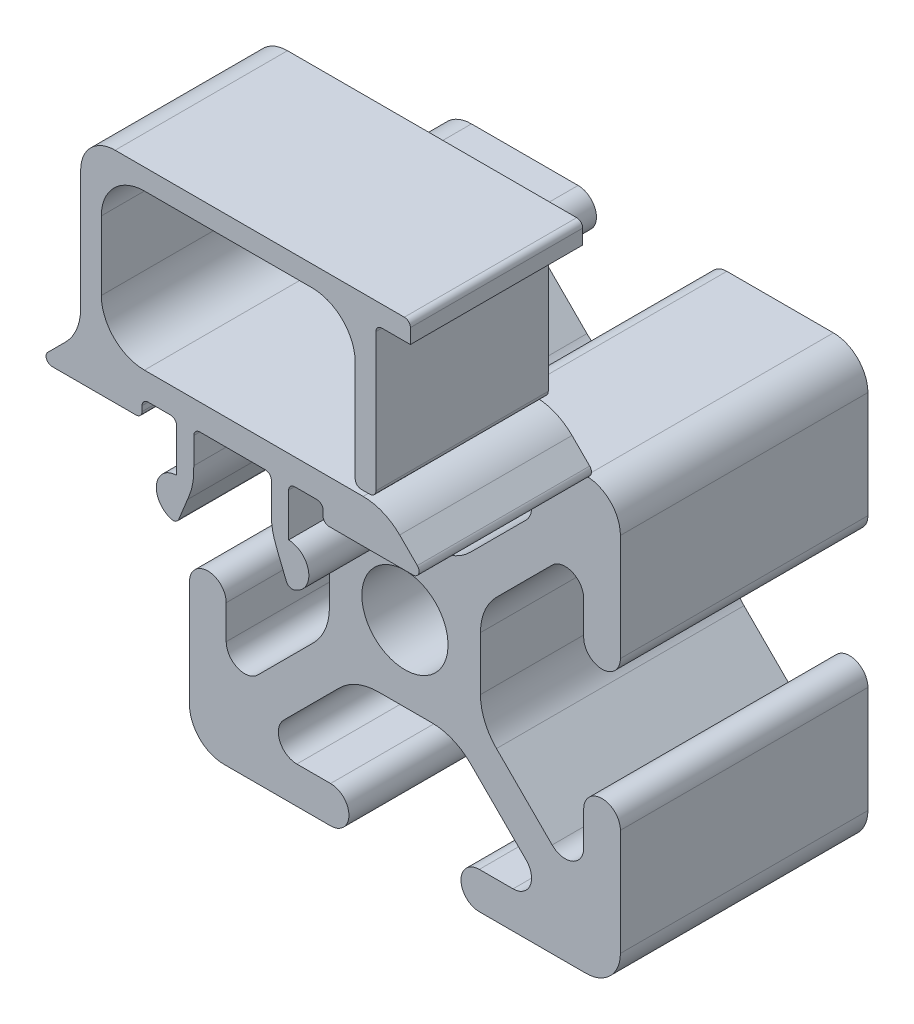
SolidWorks part; units mm, degrees
ref_plane "Front Plane" through (0, 0, 0) normal (0, 0, 1) x (1, 0, 0)
ref_plane "Top Plane" through (0, 0, 0) normal (0, 1, 0) x (1, 0, 0)
ref_plane "Right Plane" through (0, 0, 0) normal (1, 0, 0) x (0, 0, -1)
sketch "Sketch1" plane through (0, 0, 0) normal (0, 1, 0) x (1, 0, 0)
  line L0 (0, 0) -> (0, 14.3598)
other "25 series extrusions 25-2525(1)" corner treatment butt1
ref_plane "Plane1" through (0, 0, 0) normal (0, 0, -1) x (-1, 0, 0)
sketch "Sketch11" plane through (0, 0, 0) normal (0, 0, -1) x (-1, 0, 0)
  line L0 (12.5, -10.5) -> (12.5, -4.315)
  line L1 (10.37, -4.315) -> (10.37, -6.2728)
  line L2 (8.5396, -7.031) -> (5.311, -3.8024)
  line L3 (4.3811, -1.5573) -> (4.3811, 1.5573)
  line L4 (5.311, 3.8024) -> (8.5396, 7.031)
  line L5 (10.37, 6.2728) -> (10.37, 4.315)
  line L6 (12.5, 4.315) -> (12.5, 10.5)
  line L7 (10.5, 12.5) -> (4.315, 12.5)
  line L8 (4.315, 10.37) -> (6.2728, 10.37)
  line L9 (7.031, 8.5396) -> (3.8024, 5.311)
  line L10 (1.5573, 4.3811) -> (-1.5573, 4.3811)
  line L11 (-3.8024, 5.311) -> (-7.031, 8.5396)
  line L12 (-6.2728, 10.37) -> (-4.315, 10.37)
  line L13 (-4.315, 12.5) -> (-10.5, 12.5)
  line L14 (-12.5, 10.5) -> (-12.5, 4.315)
  line L15 (-10.37, 4.315) -> (-10.37, 6.2728)
  line L16 (-8.5396, 7.031) -> (-5.311, 3.8024)
  line L17 (-4.3811, 1.5573) -> (-4.3811, -1.5573)
  line L18 (-5.311, -3.8024) -> (-8.5396, -7.031)
  line L19 (-10.37, -6.2728) -> (-10.37, -4.315)
  line L20 (-12.5, -4.315) -> (-12.5, -10.5)
  line L21 (-10.5, -12.5) -> (-4.315, -12.5)
  line L22 (-4.315, -10.37) -> (-6.2728, -10.37)
  line L23 (-7.031, -8.5396) -> (-3.8024, -5.311)
  line L24 (-1.5573, -4.3811) -> (1.5573, -4.3811)
  line L25 (3.8024, -5.311) -> (7.031, -8.5396)
  line L26 (6.2728, -10.37) -> (4.315, -10.37)
  line L27 (4.315, -12.5) -> (10.5, -12.5)
  circle A0 centre (0, 0) radius 2.5
  arc A1 (10.5, -12.5) -> (12.5, -10.5) centre (10.5, -10.5) ccw
  arc A2 (12.5, -4.315) -> (10.37, -4.315) centre (11.435, -4.315) ccw
  arc A3 (8.5396, -7.031) -> (10.37, -6.2728) centre (9.2978, -6.2728) ccw
  arc A4 (4.3811, -1.5573) -> (5.311, -3.8024) centre (7.5561, -1.5573) ccw
  arc A5 (5.311, 3.8024) -> (4.3811, 1.5573) centre (7.5561, 1.5573) ccw
  arc A6 (10.37, 6.2728) -> (8.5396, 7.031) centre (9.2978, 6.2728) ccw
  arc A7 (10.37, 4.315) -> (12.5, 4.315) centre (11.435, 4.315) ccw
  arc A8 (12.5, 10.5) -> (10.5, 12.5) centre (10.5, 10.5) ccw
  arc A9 (4.315, 12.5) -> (4.315, 10.37) centre (4.315, 11.435) ccw
  arc A10 (7.031, 8.5396) -> (6.2728, 10.37) centre (6.2728, 9.2978) ccw
  arc A11 (1.5573, 4.3811) -> (3.8024, 5.311) centre (1.5573, 7.5561) ccw
  arc A12 (-3.8024, 5.311) -> (-1.5573, 4.3811) centre (-1.5573, 7.5561) ccw
  arc A13 (-6.2728, 10.37) -> (-7.031, 8.5396) centre (-6.2728, 9.2978) ccw
  arc A14 (-4.315, 10.37) -> (-4.315, 12.5) centre (-4.315, 11.435) ccw
  arc A15 (-10.5, 12.5) -> (-12.5, 10.5) centre (-10.5, 10.5) ccw
  arc A16 (-12.5, 4.315) -> (-10.37, 4.315) centre (-11.435, 4.315) ccw
  arc A17 (-8.5396, 7.031) -> (-10.37, 6.2728) centre (-9.2978, 6.2728) ccw
  arc A18 (-4.3811, 1.5573) -> (-5.311, 3.8024) centre (-7.5561, 1.5573) ccw
  arc A19 (-5.311, -3.8024) -> (-4.3811, -1.5573) centre (-7.5561, -1.5573) ccw
  arc A20 (-10.37, -6.2728) -> (-8.5396, -7.031) centre (-9.2978, -6.2728) ccw
  arc A21 (-10.37, -4.315) -> (-12.5, -4.315) centre (-11.435, -4.315) ccw
  arc A22 (-12.5, -10.5) -> (-10.5, -12.5) centre (-10.5, -10.5) ccw
  arc A23 (-4.315, -12.5) -> (-4.315, -10.37) centre (-4.315, -11.435) ccw
  arc A24 (-7.031, -8.5396) -> (-6.2728, -10.37) centre (-6.2728, -9.2978) ccw
  arc A25 (-1.5573, -4.3811) -> (-3.8024, -5.311) centre (-1.5573, -7.5561) ccw
  arc A26 (3.8024, -5.311) -> (1.5573, -4.3811) centre (1.5573, -7.5561) ccw
  arc A27 (6.2728, -10.37) -> (7.031, -8.5396) centre (6.2728, -9.2978) ccw
  arc A28 (4.315, -10.37) -> (4.315, -12.5) centre (4.315, -11.435) ccw
  point P0 (0, 0)
  dimension "D1" = 5
sketch "Sketch13" plane through (0, 0, 0) normal (0, 0, 1) x (1, 0, 0)
  line L28 (-10.5, -12.5) -> (-4.315, -12.5)
  line L29 (-4.315, -10.37) -> (-6.2728, -10.37)
  line L30 (-7.031, -8.5396) -> (-3.8024, -5.311)
  line L31 (-1.5573, -4.3811) -> (1.5573, -4.3811)
  line L32 (3.8024, -5.311) -> (7.031, -8.5396)
  line L33 (6.2728, -10.37) -> (4.315, -10.37)
  line L34 (4.315, -12.5) -> (10.5, -12.5)
  line L35 (12.5, -10.5) -> (12.5, -4.315)
  line L36 (10.37, -4.315) -> (10.37, -6.2728)
  line L37 (8.5396, -7.031) -> (5.311, -3.8024)
  line L38 (4.3811, -1.5573) -> (4.3811, 1.5573)
  line L39 (5.311, 3.8024) -> (8.5396, 7.031)
  line L40 (10.37, 6.2728) -> (10.37, 4.315)
  line L41 (12.5, 4.315) -> (12.5, 10.5)
  line L42 (10.5, 12.5) -> (4.315, 12.5)
  line L43 (4.315, 10.37) -> (6.2728, 10.37)
  line L44 (7.031, 8.5396) -> (3.8024, 5.311)
  line L45 (1.5573, 4.3811) -> (-1.5573, 4.3811)
  line L46 (-3.8024, 5.311) -> (-7.031, 8.5396)
  line L47 (-6.2728, 10.37) -> (-4.315, 10.37)
  line L48 (-4.315, 12.5) -> (-10.5, 12.5)
  line L49 (-12.5, 10.5) -> (-12.5, 4.315)
  line L50 (-10.37, 4.315) -> (-10.37, 6.2728)
  line L51 (-8.5396, 7.031) -> (-5.311, 3.8024)
  line L52 (-4.3811, 1.5573) -> (-4.3811, -1.5573)
  line L53 (-5.311, -3.8024) -> (-8.5396, -7.031)
  line L54 (-10.37, -6.2728) -> (-10.37, -4.315)
  line L55 (-12.5, -4.315) -> (-12.5, -10.5)
  line L56 (-10.5, -12.5) -> (-4.315, -12.5)
  line L57 (-4.315, -10.37) -> (-6.2728, -10.37)
  line L58 (-7.031, -8.5396) -> (-3.8024, -5.311)
  line L59 (-1.5573, -4.3811) -> (1.5573, -4.3811)
  line L60 (3.8024, -5.311) -> (7.031, -8.5396)
  line L61 (6.2728, -10.37) -> (4.315, -10.37)
  line L62 (4.315, -12.5) -> (10.5, -12.5)
  line L63 (12.5, -10.5) -> (12.5, -4.315)
  line L64 (10.37, -4.315) -> (10.37, -6.2728)
  line L65 (8.5396, -7.031) -> (5.311, -3.8024)
  line L66 (4.3811, -1.5573) -> (4.3811, 1.5573)
  line L67 (5.311, 3.8024) -> (8.5396, 7.031)
  line L68 (10.37, 6.2728) -> (10.37, 4.315)
  line L69 (12.5, 4.315) -> (12.5, 10.5)
  line L70 (10.5, 12.5) -> (4.315, 12.5)
  line L71 (4.315, 10.37) -> (6.2728, 10.37)
  line L72 (7.031, 8.5396) -> (3.8024, 5.311)
  line L73 (1.5573, 4.3811) -> (-1.5573, 4.3811)
  line L74 (-3.8024, 5.311) -> (-7.031, 8.5396)
  line L75 (-6.2728, 10.37) -> (-4.315, 10.37)
  line L76 (-4.315, 12.5) -> (-10.5, 12.5)
  line L77 (-12.5, 10.5) -> (-12.5, 4.315)
  line L78 (-10.37, 4.315) -> (-10.37, 6.2728)
  line L79 (-8.5396, 7.031) -> (-5.311, 3.8024)
  line L80 (-4.3811, 1.5573) -> (-4.3811, -1.5573)
  line L81 (-5.311, -3.8024) -> (-8.5396, -7.031)
  line L82 (-10.37, -6.2728) -> (-10.37, -4.315)
  line L83 (-12.5, -4.315) -> (-12.5, -10.5)
  arc A28 (-12.5, -10.5) -> (-10.5, -12.5) centre (-10.5, -10.5) ccw
  arc A29 (-4.315, -12.5) -> (-4.315, -10.37) centre (-4.315, -11.435) ccw
  arc A30 (-7.031, -8.5396) -> (-6.2728, -10.37) centre (-6.2728, -9.2978) ccw
  arc A31 (-1.5573, -4.3811) -> (-3.8024, -5.311) centre (-1.5573, -7.5561) ccw
  arc A32 (3.8024, -5.311) -> (1.5573, -4.3811) centre (1.5573, -7.5561) ccw
  arc A33 (6.2728, -10.37) -> (7.031, -8.5396) centre (6.2728, -9.2978) ccw
  arc A34 (4.315, -10.37) -> (4.315, -12.5) centre (4.315, -11.435) ccw
  arc A35 (10.5, -12.5) -> (12.5, -10.5) centre (10.5, -10.5) ccw
  arc A36 (12.5, -4.315) -> (10.37, -4.315) centre (11.435, -4.315) ccw
  arc A37 (8.5396, -7.031) -> (10.37, -6.2728) centre (9.2978, -6.2728) ccw
  arc A38 (4.3811, -1.5573) -> (5.311, -3.8024) centre (7.5561, -1.5573) ccw
  arc A39 (5.311, 3.8024) -> (4.3811, 1.5573) centre (7.5561, 1.5573) ccw
  arc A40 (10.37, 6.2728) -> (8.5396, 7.031) centre (9.2978, 6.2728) ccw
  arc A41 (10.37, 4.315) -> (12.5, 4.315) centre (11.435, 4.315) ccw
  arc A42 (12.5, 10.5) -> (10.5, 12.5) centre (10.5, 10.5) ccw
  arc A43 (4.315, 12.5) -> (4.315, 10.37) centre (4.315, 11.435) ccw
  arc A44 (7.031, 8.5396) -> (6.2728, 10.37) centre (6.2728, 9.2978) ccw
  arc A45 (1.5573, 4.3811) -> (3.8024, 5.311) centre (1.5573, 7.5561) ccw
  arc A46 (-3.8024, 5.311) -> (-1.5573, 4.3811) centre (-1.5573, 7.5561) ccw
  arc A47 (-6.2728, 10.37) -> (-7.031, 8.5396) centre (-6.2728, 9.2978) ccw
  arc A48 (-4.315, 10.37) -> (-4.315, 12.5) centre (-4.315, 11.435) ccw
  arc A49 (-10.5, 12.5) -> (-12.5, 10.5) centre (-10.5, 10.5) ccw
  arc A50 (-12.5, 4.315) -> (-10.37, 4.315) centre (-11.435, 4.315) ccw
  arc A51 (-8.5396, 7.031) -> (-10.37, 6.2728) centre (-9.2978, 6.2728) ccw
  arc A52 (-4.3811, 1.5573) -> (-5.311, 3.8024) centre (-7.5561, 1.5573) ccw
  arc A53 (-5.311, -3.8024) -> (-4.3811, -1.5573) centre (-7.5561, -1.5573) ccw
  arc A54 (-10.37, -6.2728) -> (-8.5396, -7.031) centre (-9.2978, -6.2728) ccw
  arc A55 (-10.37, -4.315) -> (-12.5, -4.315) centre (-11.435, -4.315) ccw
  arc A56 (-12.5, -10.5) -> (-10.5, -12.5) centre (-10.5, -10.5) ccw
  arc A57 (-4.315, -12.5) -> (-4.315, -10.37) centre (-4.315, -11.435) ccw
  arc A58 (-7.031, -8.5396) -> (-6.2728, -10.37) centre (-6.2728, -9.2978) ccw
  arc A59 (-1.5573, -4.3811) -> (-3.8024, -5.311) centre (-1.5573, -7.5561) ccw
  arc A60 (3.8024, -5.311) -> (1.5573, -4.3811) centre (1.5573, -7.5561) ccw
  arc A61 (6.2728, -10.37) -> (7.031, -8.5396) centre (6.2728, -9.2978) ccw
  arc A62 (4.315, -10.37) -> (4.315, -12.5) centre (4.315, -11.435) ccw
  arc A63 (10.5, -12.5) -> (12.5, -10.5) centre (10.5, -10.5) ccw
  arc A64 (12.5, -4.315) -> (10.37, -4.315) centre (11.435, -4.315) ccw
  arc A65 (8.5396, -7.031) -> (10.37, -6.2728) centre (9.2978, -6.2728) ccw
  arc A66 (4.3811, -1.5573) -> (5.311, -3.8024) centre (7.5561, -1.5573) ccw
  arc A67 (5.311, 3.8024) -> (4.3811, 1.5573) centre (7.5561, 1.5573) ccw
  arc A68 (10.37, 6.2728) -> (8.5396, 7.031) centre (9.2978, 6.2728) ccw
  arc A69 (10.37, 4.315) -> (12.5, 4.315) centre (11.435, 4.315) ccw
  arc A70 (12.5, 10.5) -> (10.5, 12.5) centre (10.5, 10.5) ccw
  arc A71 (4.315, 12.5) -> (4.315, 10.37) centre (4.315, 11.435) ccw
  arc A72 (7.031, 8.5396) -> (6.2728, 10.37) centre (6.2728, 9.2978) ccw
  arc A73 (1.5573, 4.3811) -> (3.8024, 5.311) centre (1.5573, 7.5561) ccw
  arc A74 (-3.8024, 5.311) -> (-1.5573, 4.3811) centre (-1.5573, 7.5561) ccw
  arc A75 (-6.2728, 10.37) -> (-7.031, 8.5396) centre (-6.2728, 9.2978) ccw
  arc A76 (-4.315, 10.37) -> (-4.315, 12.5) centre (-4.315, 11.435) ccw
  arc A77 (-10.5, 12.5) -> (-12.5, 10.5) centre (-10.5, 10.5) ccw
  arc A78 (-12.5, 4.315) -> (-10.37, 4.315) centre (-11.435, 4.315) ccw
  arc A79 (-8.5396, 7.031) -> (-10.37, 6.2728) centre (-9.2978, 6.2728) ccw
  arc A80 (-4.3811, 1.5573) -> (-5.311, 3.8024) centre (-7.5561, 1.5573) ccw
  arc A81 (-5.311, -3.8024) -> (-4.3811, -1.5573) centre (-7.5561, -1.5573) ccw
  arc A82 (-10.37, -6.2728) -> (-8.5396, -7.031) centre (-9.2978, -6.2728) ccw
  arc A83 (-10.37, -4.315) -> (-12.5, -4.315) centre (-11.435, -4.315) ccw
  dimension "D1" = 0
sketch "Sketch14" plane through (0, 0, 0) normal (0, 0, 1) x (1, 0, 0)
  line L0 (-11.315, 12.5) -> (-8.815, 15)
  line L1 (-4.315, 12.5) -> (-10.5, 12.5) construction
  line L2 (-8.815, 15) -> (8.815, 15)
  line L3 (8.815, 15) -> (11.315, 12.5)
  line L4 (10.5, 12.5) -> (4.315, 12.5) construction
  line L5 (11.315, 12.5) -> (5.25, 12.5)
  line L6 (3.25, 13.5) -> (3.25, 10.65)
  line L8 (2.25, 10.65) -> (2.25, 13.5)
  line L9 (2.25, 13.5) -> (-2.25, 13.5)
  line L10 (-2.25, 13.5) -> (-2.25, 10.65)
  line L12 (-3.25, 10.65) -> (-3.25, 13.5)
  line L13 (-5.25, 12.5) -> (-11.315, 12.5)
  line L14 (-5.25, 12.5) -> (-5.25, 13.5)
  line L15 (-5.25, 13.5) -> (-3.25, 13.5)
  line L16 (5.25, 12.5) -> (5.25, 13.5)
  line L17 (5.25, 13.5) -> (3.25, 13.5)
  line L18 (-3.25, 10.65) -> (-2.25, 10.65) construction
  line L19 (2.25, 10.65) -> (3.25, 10.65) construction
  line L20 (-2.25, 10.65) -> (-3.2236, 8.2503)
  line L21 (2.25, 10.65) -> (3.2236, 8.2503)
  line L22 (-3.2236, 9.4503) -> (-3.2236, 8.2503) construction
  line L23 (3.2236, 9.4503) -> (3.2236, 8.2503) construction
  arc A0 (-4.315, 10.37) -> (-4.315, 12.5) centre (-4.315, 11.435) ccw construction
  arc A1 (-3.25, 10.65) -> (-3.2236, 8.2503) centre (-3.2236, 9.4503) ccw
  arc A2 (3.2236, 8.2503) -> (3.25, 10.65) centre (3.2236, 9.4503) ccw
  arc A3 (4.315, 12.5) -> (4.315, 10.37) centre (4.315, 11.435) ccw construction
  dimension "D5" = 1.2
  dimension "D1" = 7
  dimension "D2" = 7
  dimension "D4" = 45
  dimension "D8" = 2
  dimension "D9" = 1
  dimension "D7" = 2
  dimension "D10" = 1
  dimension "D11" = 2.85
  dimension "D3" = 1.5
extrude "Boss-Extrude1" add sketch "Sketch14" along normal blind 10 separate body
sketch "Sketch15" plane through (0, 0, 0) normal (0, 0, 1) x (1, 0, 0)
  line L0 (-8.815, 15) -> (-8.815, 25.2)
  line L1 (-8.815, 25.2) -> (10.315, 25.2)
  line L2 (8.315, 24) -> (8.315, 15.3)
  line L3 (8.315, 15.3) -> (7.115, 15.3)
  line L4 (7.115, 15.3) -> (7.115, 24)
  line L5 (7.115, 24) -> (-7.615, 24)
  line L6 (-7.615, 24) -> (-7.615, 15)
  line L7 (8.815, 15) -> (-8.815, 15) construction
  line L8 (-7.615, 15) -> (-8.815, 15)
  line L12 (8.315, 24) -> (10.315, 24)
  line L13 (10.315, 25.2) -> (10.315, 24)
  dimension "D8" = 2
  dimension "D1" = 1.2
  dimension "D2" = 1.2
  dimension "D3" = 0.3
  dimension "D4" = 1.2
  dimension "D6" = 0.5
  dimension "D5" = 9
  dimension "D7" = 1.2
extrude "Boss-Extrude3" add sketch "Sketch15" along normal up to surface (10 mm away) up to face at (0, 12.2264, 10)
fillet "r0.35" radius 0.35 16 edges at (11.315, 12.5, 5) (-11.315, 12.5, 5) (-5.25, 12.5, 5) (5.25, 12.5, 5) (-5.25, 13.5, 5) (-3.25, 13.5, 5) (-2.25, 13.5, 5) (2.25, 13.5, 5) (3.25, 13.5, 5) (5.25, 13.5, 5) (3.2236, 8.2503, 5) (-3.2236, 8.2503, 5) (7.115, 15.3, 5) (8.315, 15.3, 5) (10.315, 25.2, 5) (8.315, 24, 5)
fillet "r5.0" radius 5 2 edges at (2.25, 10.65, 5) (-2.25, 10.65, 5) curvature continuous yes
fillet "Fillet2" radius 2.5 3 edges at (-7.615, 15, 5) (-7.615, 24, 5) (7.115, 24, 5)
fillet "r3.0" radius 3 2 edges at (8.815, 15, 5) (-8.815, 15, 5)
fillet "Fillet4" radius 2 1 edges at (-8.815, 25.2, 5)
equation "\"D2@Sketch14\"=\"D1@Sketch14\""
equation "\"D7@Sketch14\"=\"D8@Sketch14\""
equation "\"D10@Sketch14\"=\"D6@Sketch14\""
equation "\"GAP\"=9"
equation "\"D5@Sketch15\"=\"GAP\""
equation "\"GAP_RAD\"= IIF ( \"GAP\" > 5 , 2.5 , \"GAP\" / 2 )"
equation "\"D2@Sketch15\"=\"D1@Sketch15\""
equation "\"D7@Sketch15\"=\"D1@Sketch15\""
